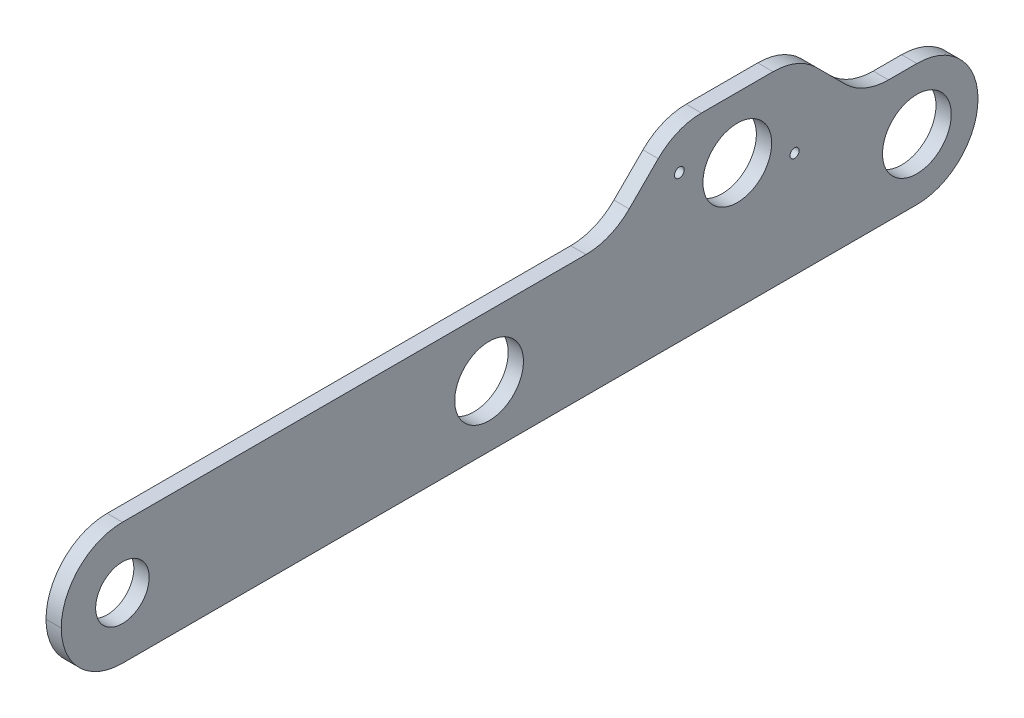
SolidWorks part; units mm, degrees
ref_plane "Front Plane" through (0, 0, 0) normal (0, 0, 1) x (1, 0, 0)
ref_plane "Top Plane" through (0, 0, 0) normal (0, 1, 0) x (1, 0, 0)
ref_plane "Right Plane" through (0, 0, 0) normal (1, 0, 0) x (0, 0, -1)
sketch "Sketch1" plane through (0, 0, 0) normal (1, 0, 0) x (0, 0, -1)
  line L0 (0, 0) -> (0, 50.8)
  line L1 (0, 55) -> (0, -55) construction
  line L2 (0, 50.8) -> (228.6, 50.8)
  line L3 (228.6, 50.8) -> (255.5408, 77.7408)
  line L4 (255.5408, 77.7408) -> (306.3408, 77.7408)
  line L5 (306.3408, 77.7408) -> (333.2815, 50.8)
  line L6 (333.2815, 50.8) -> (381, 50.8)
  line L7 (381, 50.8) -> (381, 0)
  line L8 (55, 0) -> (-55, 0) construction
  line L9 (381, 0) -> (0, 0)
  circle A0 centre (25.4, 25.4) radius 11.1125
  circle A2 centre (280.9575, 52.3408) radius 14.2875
  circle A3 centre (355.6, 25.4) radius 14.2875
  circle A4 centre (177.8, 25.4) radius 14.2875
  circle A5 centre (304.763, 43.9557) radius 1.9035
  circle A6 centre (256.8768, 60.9131) radius 2.0193
  dimension "D8" = 22.225
  dimension "D11" = 28.575
  dimension "D14" = 28.575
  dimension "D17" = 28.575
  dimension "D1" = 50.8
  dimension "D2" = 228.6
  dimension "D3" = 381
  dimension "D4" = 38.1
  dimension "D5" = 38.1
  dimension "D6" = 50.8
  dimension "D7" = 50.8
  dimension "D9" = 25.4
  dimension "D10" = 25.4
  dimension "D12" = 25.4
  dimension "D13" = 52.324
  dimension "D15" = 25.4
  dimension "D16" = 25.4
  dimension "D18" = 152.4
extrude "Boss-Extrude1" add sketch "Sketch1" along normal blind 6.35
fillet "Fillet1" radius 25.4 8 edges at (3.175, 50.8, -228.6) (3.175, 50.8, -333.2815) (3.175, 77.7408, -306.3408) (3.175, 77.7408, -255.5408) (3.175, 0, -381) (3.175, 50.8, -381) (3.175, 0, 0) (3.175, 50.8, 0)
